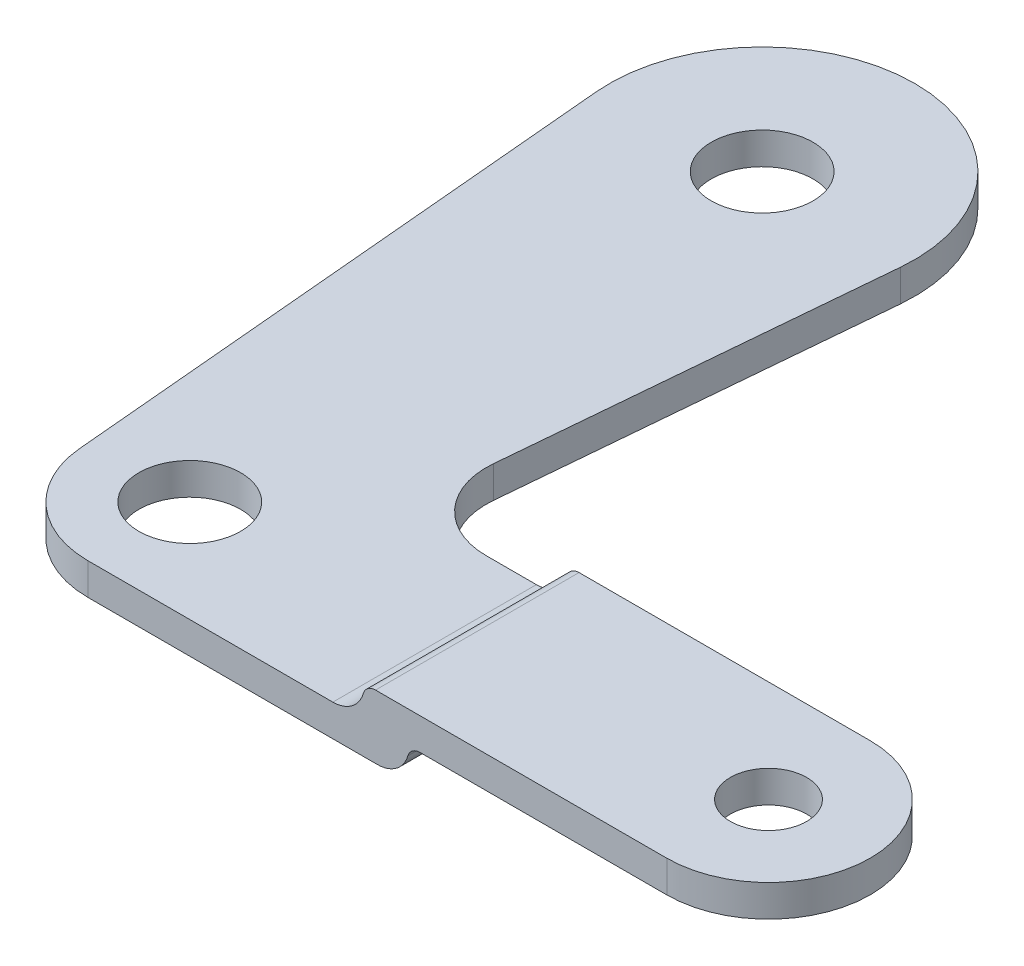
SolidWorks part; units mm, degrees
ref_plane "Front Plane" through (0, 0, 0) normal (0, 0, 1) x (1, 0, 0)
ref_plane "Top Plane" through (0, 0, 0) normal (0, 1, 0) x (1, 0, 0)
ref_plane "Right Plane" through (0, 0, 0) normal (1, 0, 0) x (0, 0, -1)
sketch "Sketch1" plane through (0, 0, 0) normal (0, 1, 0) x (1, 0, 0)
  line L0 (45.5, 0) -> (0, 0) construction
  line L1 (0, 0) -> (0, 45) construction
  line L2 (45.5, 8) -> (45.5, -8) construction
  line L3 (45.5, -8) -> (0, -8)
  line L4 (-11.9525, 43.9333) -> (-7.9683, -0.7111)
  line L5 (11.9525, 43.9333) -> (9.3288, 14.5333)
  line L6 (45.5, 8) -> (15.305, 8)
  line L7 (22.75, 8) -> (22.75, -8)
  circle A0 centre (45.5, 0) radius 3
  circle A1 centre (0, 0) radius 4
  circle A2 centre (0, 45) radius 4
  arc A3 (45.5, 8) -> (45.5, -8) centre (45.5, 0) cw
  arc A4 (11.9524, 43.9325) -> (-11.9525, 43.9333) centre (0, 45) ccw
  arc A5 (0, -8) -> (-7.9683, -0.7111) centre (0, 0) cw
  arc A6 (15.305, 8) -> (9.3288, 14.5333) centre (15.305, 14) cw
  dimension "D3" = 6
  dimension "D4" = 8
  dimension "D5" = 8
  dimension "D6" = 8
  dimension "D7" = 12
  dimension "D8" = 6
  dimension "D1" = 45.5
  dimension "D2" = 45
extrude "Boss-Extrude1" add sketch "Sketch1" along normal blind 2.5 contours A3 L6 L7 L3 A0 region at (36.7914, 0, 0)
extrude "Boss-Extrude2" add sketch "Sketch1<3>" along normal blind 2.5 from surface separate body contours L6 A6 L5 A4 L4 A5 L3 L7 A2 A1 region at (2.7322, 0, -21.9361) starting at face at (36.125, 2.5, 0)
sketch "Sketch1<3>" plane through (0, 0, 0) normal (0, 1, 0) x (1, 0, 0) same geometry as "Sketch1"
sketch "Sketch2" plane through (0, 0, 8) normal (0, 0, 1) x (1, 0, 0)
  line L0 (19.25, 5) -> (19.25, 2.5)
  line L1 (26.25, 2.5) -> (26.25, 0)
  line L2 (26.25, 0) -> (22.6041, 0)
  line L3 (26.25, 2.5) -> (26.1041, 2.5)
  line L4 (22.75, 5) -> (19.25, 5)
  line L5 (45.5, 0) -> (22.75, 0) construction
  line L7 (45.5, 2.5) -> (22.75, 2.5) construction
  line L8 (0, 5) -> (22.75, 5) construction
  line L9 (0, 2.5) -> (22.75, 2.5) construction
  arc A0 (22.75, 5) -> (25.1458, 3.2143) centre (22.75, 2.5) cw
  arc A1 (19.25, 2.5) -> (21.6458, 0.7143) centre (19.25, 0) cw
  arc A2 (21.6458, 0.7143) -> (22.6041, 0) centre (22.6041, 1) ccw
  arc A3 (25.1458, 3.2143) -> (26.1041, 2.5) centre (26.1041, 3.5) ccw
  line M12 (45.5, 2.5) -> (22.75, 2.5)
  line M13 (22.75, 2.5) -> (22.75, 0)
  dimension "D1" = 1
  dimension "D3" = 2.5
  dimension "D4" = 2.5
  dimension "D2" = 3.5
extrude "Boss-Extrude3" add sketch "Sketch2" along direction (0, 0, 1) on the side against the normal blind 16 contours A3 A0 L4 L0 A1 A2 L2 M13 M12 region at (22.008, 3.22, 8)
mirror "Mirror4" about plane through (0, 0, 0) normal (0, 1, 0) of bodies 103
delete or keep bodies "Body-Delete/Keep 1" type delete bodies bodies 103
